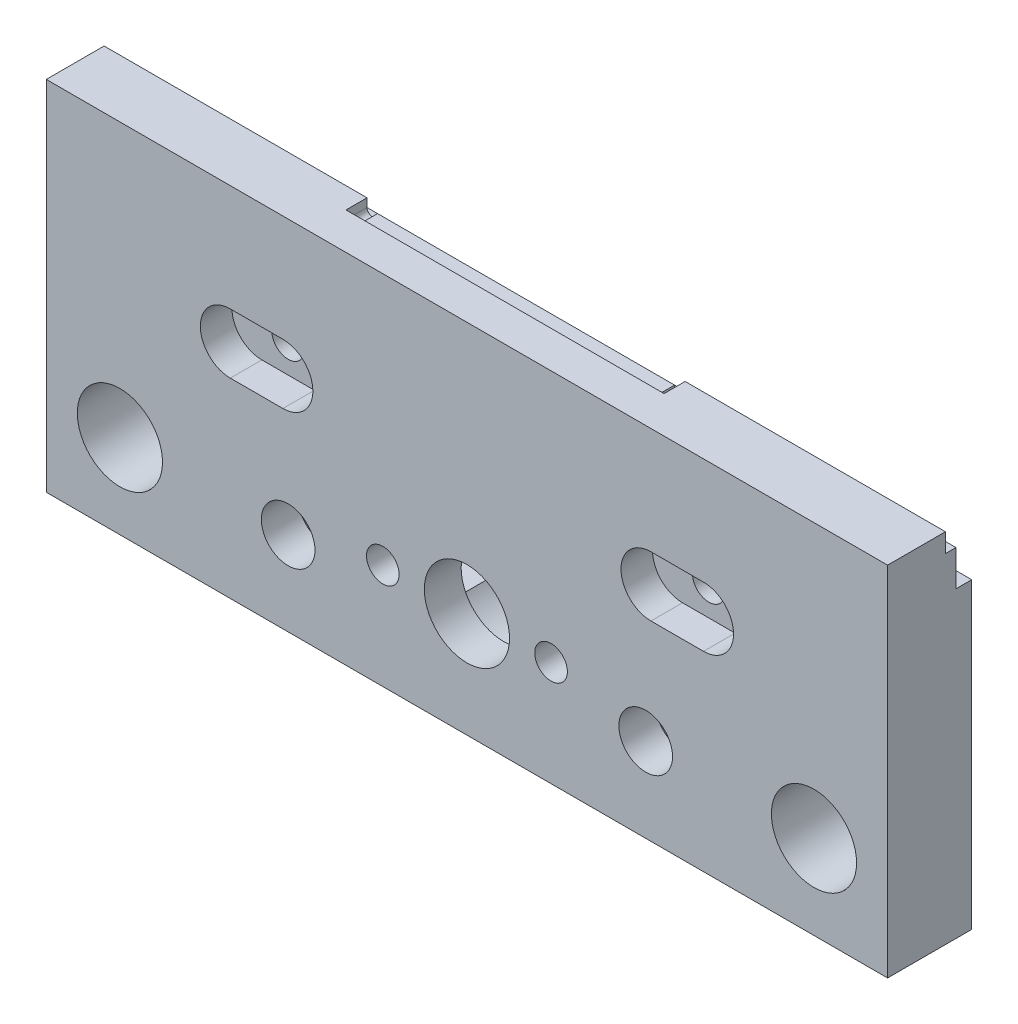
SolidWorks part; units mm, degrees
ref_plane "前视基准面" through (0, 0, 0) normal (0, 0, 1) x (1, 0, 0)
ref_plane "上视基准面" through (0, 0, 0) normal (0, 1, 0) x (1, 0, 0)
ref_plane "右视基准面" through (0, 0, 0) normal (1, 0, 0) x (0, 0, -1)
sketch "前视图草图" plane through (0, 0, 0) normal (0, 0, 1) x (1, 0, 0)
  line L0 (0, 0) -> (44.4821, 0) construction
  line L1 (0, 0) -> (0, 28.3185) construction
sketch "草图2" plane through (0, 0, 0) normal (0, 0, 1) x (1, 0, 0)
  line L0 (0, 0) -> (80, 0)
  line L1 (-200000, 0) -> (200044.4821, 0) construction
  line L2 (80, 0) -> (80, 34)
  line L3 (80, 34) -> (0, 34)
  line L4 (0, -200000) -> (0, 200028.3185) construction
  line L5 (0, 34) -> (0, 0)
  circle A0 centre (7, 8) radius 4.05
  circle A1 centre (40, 10) radius 4.05
  circle A2 centre (73, 8) radius 4.05
  dimension "D3" = 8
  dimension "D5" = 10
  dimension "D9" = 8.1
  dimension "D10" = 8.1
  dimension "D11" = 8.1
  dimension "D1" = 34
  dimension "D2" = 80
  dimension "D4" = 7
  dimension "D6" = 7
  dimension "D7" = 8
  dimension "D8" = 40
extrude "凸台-拉伸1" add sketch "草图2" along normal blind 8
sketch "草图3" plane through (0, 0, 8) normal (0, 0, 1) x (1, 0, 0)
  line L0 (16.088, 8) -> (31.4805, 8) construction
  line L1 (7, 8) -> (7, 16.8386) construction
  line L2 (73, 8) -> (73, 16.5917) construction
  line L4 (-200000, 0) -> (200044.4821, 0) construction
  circle A2 centre (23, 8) radius 2.55
  circle A3 centre (57, 8) radius 2.55
  dimension "D4" = 5.1
  dimension "D5" = 5.1
  dimension "D1" = 8
  dimension "D2" = 16
  dimension "D3" = 16
extrude "切除-拉伸1" cut sketch "草图3" against normal through all
sketch "草图4" plane through (80, 0, 0) normal (1, 0, 0) x (0, 0, -1)
  line L1 (0, -200000) -> (0, 200028.3185) construction
  line L2 (-1.5, 32.2) -> (-2.5, 32.2)
  line L3 (-2.5, 32.2) -> (-2.5, 34)
  line L4 (-8, 34) -> (0, 34) construction
  line L5 (-2.5, 34) -> (0, 34)
  line L6 (-1.5, 32.2) -> (-1.5, 28.8)
  line L7 (-1.5, 28.8) -> (0, 28.8)
  line L8 (0, 28.8) -> (0, 34)
  dimension "D1" = 3.4
  dimension "D2" = 2.5
  dimension "D3" = 1.5
  dimension "D4" = 1.8
extrude "切除-拉伸2" cut sketch "草图4" against normal through all
sketch "草图5" plane through (0, 0, 8) normal (0, 0, 1) x (1, 0, 0)
  line L0 (40, 10) -> (56.5376, 10) construction
  circle A0 centre (40, 10) radius 8 construction
  circle A1 centre (48, 10) radius 1.55
  circle A2 centre (32, 10) radius 1.55
  dimension "D1" = 3.1
  dimension "D2" = 3.1
  dimension "D3" = 16
extrude "切除-拉伸3" cut sketch "草图5" against normal through all
sketch "草图7" plane through (0, 0, 0) normal (0, 0, -1) x (-1, 0, 0)
  line L0 (-40, 12) -> (-40, -8.3696) construction
  line L1 (-23, 10) -> (-23, -2.3368) construction
  line L2 (200000, 0) -> (-200044.4821, 0) construction
  line L6 (-27.05, 10) -> (-27.05, 2.5)
  line L7 (-29.55, 0) -> (-16.45, 0)
  line L8 (-18.95, 2.5) -> (-18.95, 10)
  line L9 (-23, 8) -> (-23, 15.9045) construction
  line L13 (0, -200000) -> (0, 200028.3185) construction
  line L14 (-57, 8) -> (-57, 15.9045) construction
  line L15 (-57, 10) -> (-57, -2.3368) construction
  line L16 (-61.05, 2.5) -> (-61.05, 10)
  line L17 (-50.45, 0) -> (-63.55, 0)
  line L18 (-52.95, 10) -> (-52.95, 2.5)
  arc A1 (-18.95, 10) -> (-27.05, 10) centre (-23, 10) ccw
  arc A4 (-29.55, 0) -> (-27.05, 2.5) centre (-29.55, 2.5) ccw
  arc A5 (-18.95, 2.5) -> (-16.45, 0) centre (-16.45, 2.5) ccw
  arc A7 (-61.05, 2.5) -> (-63.55, 0) centre (-63.55, 2.5) cw
  arc A8 (-50.45, 0) -> (-52.95, 2.5) centre (-50.45, 2.5) cw
  arc A9 (-61.05, 10) -> (-52.95, 10) centre (-57, 10) cw
  dimension "D1" = 40
  dimension "D4" = 8.1
  dimension "D7" = 2.5
  dimension "D8" = 2.5
  dimension "D3" = 10
extrude "切除-拉伸4" cut sketch "草图7" against normal blind 4.5
sketch "草图8" plane through (0, 0, 0) normal (0, 0, -1) x (-1, 0, 0)
  line L0 (-40, 10) -> (-57.3165, 10) construction
  line L1 (-40, 20) -> (-40, 35.6562) construction
  line L2 (-30.5, 12.85) -> (-49.5, 12.85)
  line L3 (-49.5, 7.15) -> (-30.5, 7.15)
  line L4 (200000, 0) -> (-200044.4821, 0) construction
  arc A0 (-30.5, 7.15) -> (-30.5, 12.85) centre (-30.5, 10) ccw
  arc A1 (-49.5, 12.85) -> (-49.5, 7.15) centre (-49.5, 10) ccw
  dimension "D1" = 5.7
  dimension "D2" = 9.5
  dimension "D3" = 9.5
  dimension "D4" = 10
extrude "切除-拉伸5" cut sketch "草图8" against normal blind 4.5
sketch "草图11" plane through (0, 0, 0) normal (0, 0, -1) x (-1, 0, 0)
  line L0 (-40, 20) -> (-58.6363, 20) construction
  line L1 (-80, 0) -> (-80, 28.8) construction
  line L2 (0, -200000) -> (0, 200028.3185) construction
  line L3 (-40, 20) -> (-40, 13.5744) construction
  line L4 (-28.772, 21) -> (-45.9396, 21) construction
  circle A0 centre (-60, 21) radius 1.55
  circle A1 centre (-20, 21) radius 1.55
  point P23 (-40, 20)
  dimension "D1" = 3.1
  dimension "D2" = 3.1
  dimension "D3" = 20
  dimension "D4" = 20
  dimension "D5" = 1
sketch "草图20" plane through (0, 0, 0) normal (0, 0, -1) x (-1, 0, 0)
  circle A0 centre (-40, 10) radius 5.5
  dimension "D1" = 11
extrude "切除-拉伸12" cut sketch "草图20" against normal blind 4.5
extrude "切除-拉伸7" cut sketch "草图11" against normal through all contours A0 | A1 region at (60, 21, 0) region at (20, 21, 0)
sketch "草图12" plane through (0, 0, 0) normal (0, 0, -1) x (-1, 0, 0)
  line L0 (-62.5, 18.15) -> (-57.5, 18.15)
  line L1 (-57.5, 23.85) -> (-62.5, 23.85)
  line L4 (-40, 20) -> (-42.9914, 20) construction
  line L5 (-39.1423, 21) -> (-43.2672, 21) construction
  line L6 (-60, 21) -> (-60, 25.2385) construction
  line L7 (-20, 21) -> (-20, 26.1603) construction
  line L8 (-40, 20) -> (-40, 24.3689) construction
  line L9 (-17.5, 23.85) -> (-22.5, 23.85)
  line L10 (-22.5, 18.15) -> (-17.5, 18.15)
  arc A0 (-62.5, 23.85) -> (-62.5, 18.15) centre (-62.5, 21) ccw
  arc A1 (-57.5, 18.15) -> (-57.5, 23.85) centre (-57.5, 21) ccw
  arc A4 (-17.5, 18.15) -> (-17.5, 23.85) centre (-17.5, 21) ccw
  arc A5 (-22.5, 23.85) -> (-22.5, 18.15) centre (-22.5, 21) ccw
  point P16 (-38, 21)
  point P28 (-40, 21)
  dimension "D2" = 1
  dimension "D3" = 5
  dimension "D4" = 2.5
  dimension "D1" = 2
extrude "切除-拉伸8" cut sketch "草图12" against normal blind 3
sketch "草图15" plane through (0, 0, 8) normal (0, 0, 1) x (1, 0, 0)
  line L2 (57.5, 18.15) -> (62.5, 18.15)
  line L3 (62.5, 23.85) -> (57.5, 23.85)
  line L4 (57.5, 18.15) -> (62.5, 18.15)
  line L5 (62.5, 23.85) -> (57.5, 23.85)
  line L6 (22.5, 23.85) -> (17.5, 23.85)
  line L7 (17.5, 18.15) -> (22.5, 18.15)
  line L8 (22.5, 23.85) -> (17.5, 23.85)
  line L9 (17.5, 18.15) -> (22.5, 18.15)
  arc A2 (62.5, 18.15) -> (62.5, 23.85) centre (62.5, 21) ccw
  arc A3 (57.5, 23.85) -> (57.5, 18.15) centre (57.5, 21) ccw
  arc A4 (62.5, 18.15) -> (62.5, 23.85) centre (62.5, 21) ccw
  arc A5 (57.5, 23.85) -> (57.5, 18.15) centre (57.5, 21) ccw
  arc A6 (17.5, 23.85) -> (17.5, 18.15) centre (17.5, 21) ccw
  arc A7 (22.5, 18.15) -> (22.5, 23.85) centre (22.5, 21) ccw
  arc A8 (17.5, 23.85) -> (17.5, 18.15) centre (17.5, 21) ccw
  arc A9 (22.5, 18.15) -> (22.5, 23.85) centre (22.5, 21) ccw
  dimension "D1" = 0
  dimension "D2" = 0
extrude "切除-拉伸9" cut sketch "草图15" against normal blind 3
sketch "草图19" plane through (0, 0, 2.5) normal (0, 0, -1) x (-1, 0, 0)
  line L0 (0, 34) -> (-80, 34) construction
  line L1 (-25, 34) -> (-55.2479, 34)
  line L2 (-25, 34) -> (-25, 33.2)
  line L3 (-26, 33.2) -> (-54.2479, 33.2)
  line L4 (-55.2479, 34) -> (-55.2479, 33.2)
  line L5 (0, -200000) -> (0, 200028.3185) construction
  line L7 (0, 32.2) -> (-80, 32.2) construction
  line L8 (-56.3335, 32.7) -> (-52.9089, 32.7) construction
  line L9 (-55.2479, 1028.5823) -> (-55.2479, 33.2) construction
  line L10 (-25, 1028.5823) -> (-25, 32.7) construction
  line L11 (-55.2479, 32.7) -> (-55.2479, -973.3) construction
  line L12 (-25, 32.7) -> (-25, -973.3) construction
  arc A3 (-55.2479, 33.2) -> (-54.2479, 33.2) centre (-54.7479, 33.2) ccw
  arc A6 (-26, 33.2) -> (-25, 33.2) centre (-25.5, 33.2) ccw
  dimension "D3" = 1
  dimension "D4" = 1
  dimension "D2" = 0.8
  dimension "D1" = 0.5
  dimension "D9" = 25
extrude "切除-拉伸11" cut sketch "草图19" against normal blind 2
